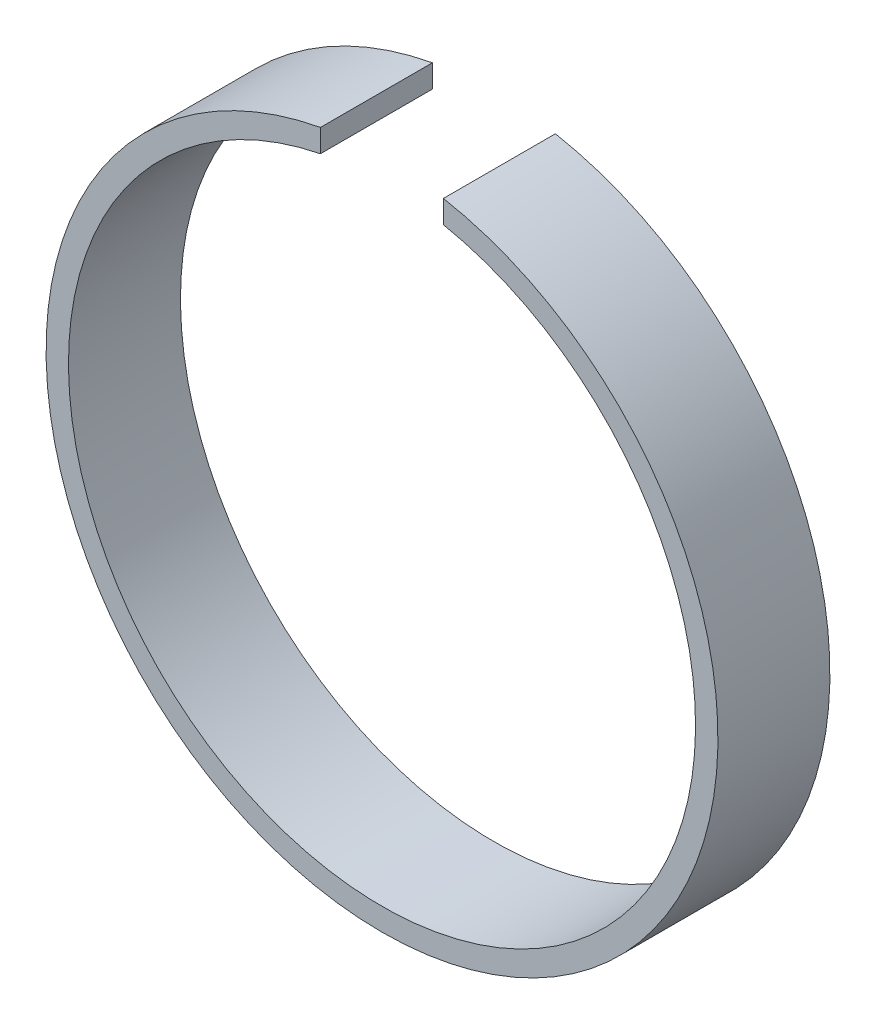
SolidWorks part; units mm, degrees
ref_plane "Front Plane" through (0, 0, 0) normal (0, 0, 1) x (1, 0, 0)
ref_plane "Top Plane" through (0, 0, 0) normal (0, 1, 0) x (1, 0, 0)
ref_plane "Right Plane" through (0, 0, 0) normal (1, 0, 0) x (0, 0, -1)
sketch "Sketch2" plane through (0, 0, 0) normal (0, 0, 1) x (1, 0, 0)
  line L1 (5.4833, 27.4579) -> (5.4833, 29.4946)
  line L8 (-5.5, 29.4915) -> (-5.5, 27.4545)
  arc A3 (-5.5, 27.4545) -> (5.4833, 27.4579) centre (0, 0) ccw
  arc A4 (-5.5, 29.4915) -> (5.4833, 29.4946) centre (0, 0) ccw
  point P4 (0, 27.7681)
  point P5 (5.3559, 27.4711)
  point P6 (5.5, 26.2792)
  point P7 (0, 0)
extrude "Boss-Extrude1" add sketch "Sketch2" along normal blind 10
